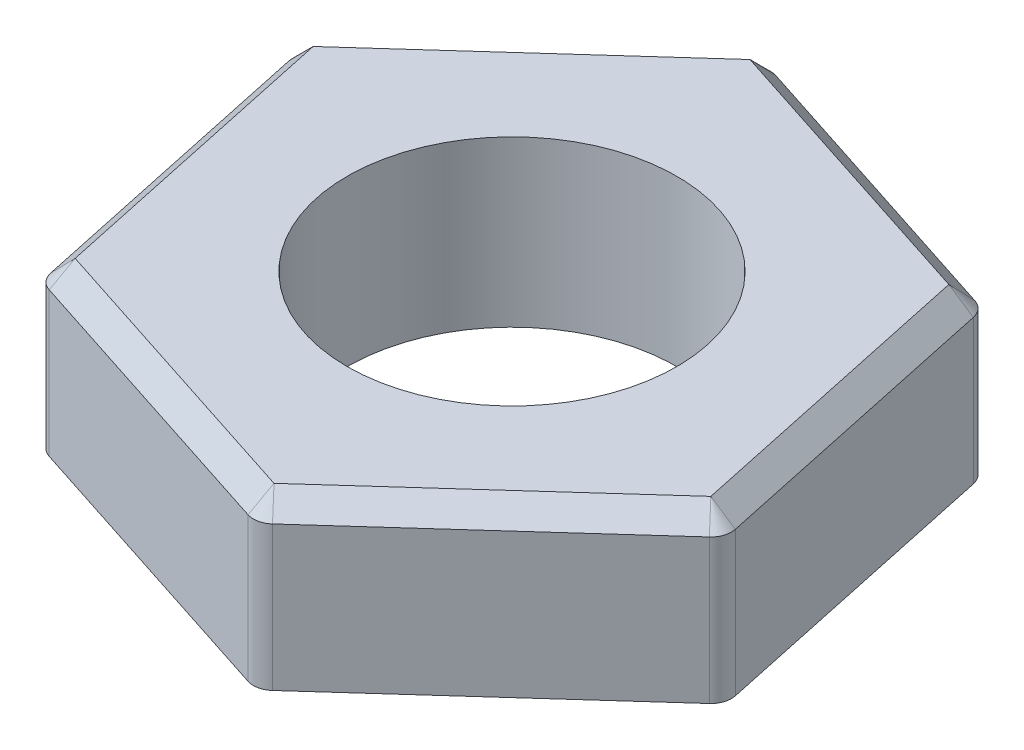
SolidWorks part; units mm, degrees
material "1060 Alloy"
ref_plane "Front Plane" through (0, 0, 0) normal (0, 0, 1) x (1, 0, 0)
ref_plane "Top Plane" through (0, 0, 0) normal (0, 1, 0) x (1, 0, 0)
ref_plane "Right Plane" through (0, 0, 0) normal (1, 0, 0) x (0, 0, -1)
sketch "Sketch1" plane through (0, 0, 0) normal (0, 1, 0) x (1, 0, 0)
  line L1 (6.0031, 5.4126) -> (-1.6859, 7.9051)
  line L2 (-1.6859, 7.9051) -> (-7.689, 2.4925)
  line L3 (-7.689, 2.4925) -> (-6.0031, -5.4126)
  line L4 (-6.0031, -5.4126) -> (1.6859, -7.9051)
  line L5 (1.6859, -7.9051) -> (7.689, -2.4925)
  line L6 (7.689, -2.4925) -> (6.0031, 5.4126)
  circle A0 centre (0, 0) radius 7 construction
  dimension "D1" = 14
extrude "Boss-Extrude1" add sketch "Sketch1" along normal blind 4
fillet "Fillet1" radius 0.5 6 edges at (7.689, 2, 2.4925) (-6.0031, 2, 5.4126) (-7.689, 2, -2.4925) (-1.6859, 2, -7.9051) (6.0031, 2, -5.4126) (1.6859, 2, 7.9051)
chamfer "Chamfer1" distance 0.5 angle 45 12 edges at (2.1586, 4, -6.6589) (-1.6698, 4, -7.8295) (5.9456, 4, -5.3608) (-4.6875, 4, -5.1988) (6.846, 4, -1.46) (-7.6154, 4, -2.4687) (7.6154, 4, 2.4687) (-6.846, 4, 1.46) (4.6875, 4, 5.1988) (-5.9456, 4, 5.3608) (1.6698, 4, 7.8295) (-2.1586, 4, 6.6589)
sketch "Sketch2" plane through (0, 4, 0) normal (0, 1, 0) x (1, 0, 0)
  circle A0 centre (0, 0) radius 4
  dimension "D1" = 8
extrude "Cut-Extrude1" cut sketch "Sketch2" against normal blind 4 and the other way blind 4
